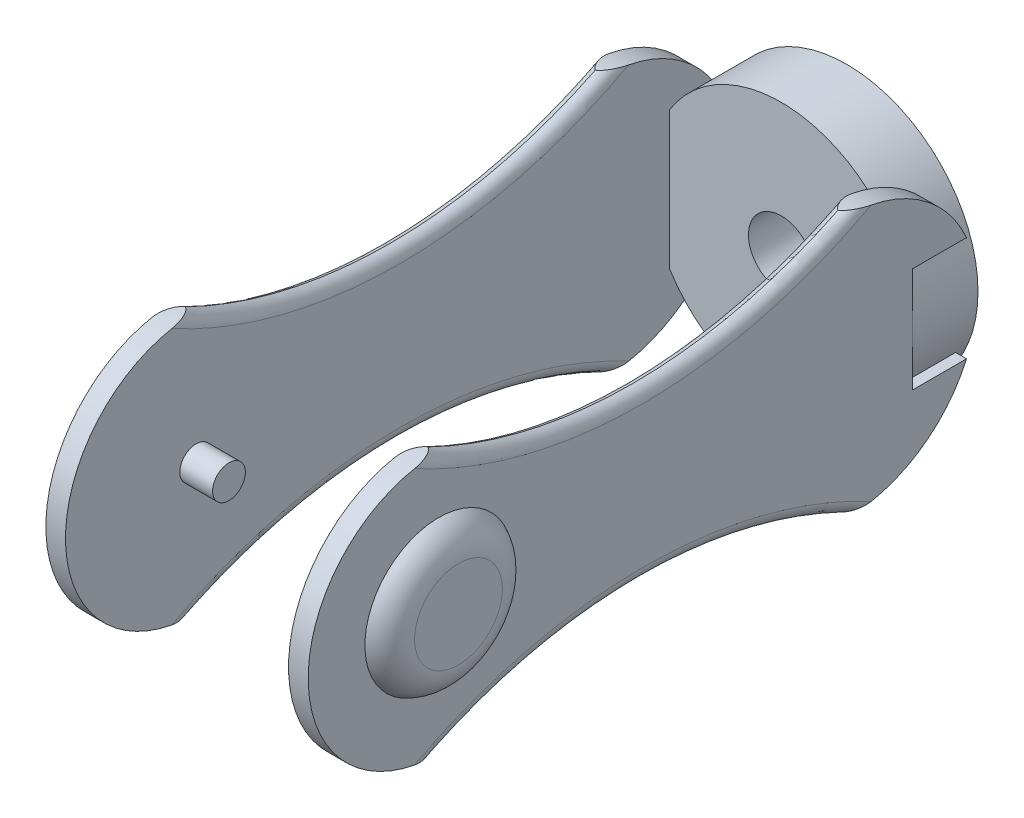
SolidWorks part; units mm, degrees
ref_plane "Front Plane" through (0, 0, 0) normal (0, 0, 1) x (1, 0, 0)
ref_plane "Top Plane" through (0, 0, 0) normal (0, 1, 0) x (1, 0, 0)
ref_plane "Right Plane" through (0, 0, 0) normal (1, 0, 0) x (0, 0, -1)
sketch "Sketch2" plane through (0, 0, 0) normal (0, 0, 1) x (1, 0, 0)
  circle A0 centre (0, 0) radius 5
  circle A1 centre (0, 0) radius 20
  dimension "D1" = 10
  dimension "D2" = 40
extrude "Boss-Extrude1" add sketch "Sketch2" along normal blind 10
ref_plane "Plane1" through (20, 0, 0) normal (1, 0, 0) x (0, 0, -1)
ref_plane "Plane2" through (-20, 0, 0) normal (-1, 0, 0) x (0, 0, 1)
sketch "Sketch4" plane through (20, 0, 0) normal (1, 0, 0) x (0, 0, -1)
  line L1 (-82.208, 19.9181) -> (-19.9909, 19.9181)
  line L2 (-82.208, -19.9181) -> (-19.9909, -19.9181)
  line L4 (-10, 8) -> (-1.7499, 8)
  line L6 (-10, -8) -> (-1.7499, -8)
  line L7 (-10, 8) -> (-10, -8)
  line L8 (-10, 20) -> (-10, -20) construction
  arc A0 (-82.208, 19.9181) -> (-82.208, -19.9181) centre (-82.208, 0) ccw
  arc A1 (-19.9909, -19.9181) -> (-1.7499, -8) centre (-19.9909, 0) ccw
  arc A2 (-1.7499, 8) -> (-19.9909, 19.9181) centre (-19.9909, 0) ccw
  point P3 (-51.0994, 0)
extrude "Boss-Extrude2" add sketch "Sketch4" against normal blind 3
pattern_circular "CirPattern1" count 2 over 360 about axis through (0, 0, 10) along (0, 0, 1) of "Boss-Extrude2"
sketch "Sketch5" plane through (-17, 0, 0) normal (1, 0, 0) x (0, 0, -1)
  circle A0 centre (-82.208, 0) radius 2.5
  dimension "D1" = 5
extrude "Boss-Extrude3" add sketch "Sketch5" along normal blind 5
sketch "Sketch6" plane through (17, 0, 0) normal (-1, 0, 0) x (0, 0, 1)
  circle A0 centre (82.208, 0) radius 2.5
  dimension "D1" = 5
extrude "Boss-Extrude4" add sketch "Sketch6" along normal blind 5
sketch "Sketch7" plane through (20, 0, 0) normal (1, 0, 0) x (0, 0, -1)
  line L0 (-82.208, -19.9181) -> (-19.9909, -19.9181) construction
  line L1 (-82.208, 19.9181) -> (-19.9909, 19.9181)
  line L2 (-82.208, -19.9181) -> (-19.9909, -19.9181)
  arc A0 (-82.208, 19.9181) -> (-19.9909, 19.9181) centre (-51.0994, 83.7648) ccw
  arc A1 (-82.208, -19.9181) -> (-19.9909, -19.9181) centre (-51.0994, -85.0834) cw
  arc A2 (-19.9909, -19.9181) -> (-1.7499, -8) centre (-19.9909, 0) ccw construction
extrude "Cut-Extrude1" cut sketch "Sketch7" against normal blind 147
fillet "Fillet1" radius 2 7 edges at (-20, -12.8736, 51.0994) (-17, -12.8736, 51.0994) (-17, 12.7427, 51.0994) (-20, 12.7427, 51.0994) (17, 12.7427, 51.0994) (20, -12.8736, 51.0994) (20, 12.7427, 51.0994)
sketch "Sketch8" plane through (20, 0, 0) normal (1, 0, 0) x (0, 0, -1)
  circle A0 centre (-82.208, 0) radius 11.2743
  dimension "D1" = 22.5486
extrude "Boss-Extrude5" add sketch "Sketch8" along normal blind 3
fillet "Fillet2" radius 5 1 edges at (23, 0, 70.9337)
sketch "Sketch9" plane through (-20, 0, 0) normal (-1, 0, 0) x (0, 0, 1)
  circle A0 centre (82.208, 0) radius 11.275
  dimension "D1" = 22.55
extrude "Boss-Extrude6" add sketch "Sketch9" along normal blind 3
fillet "Fillet3" radius 5 1 edges at (-23, 0, 93.483)
